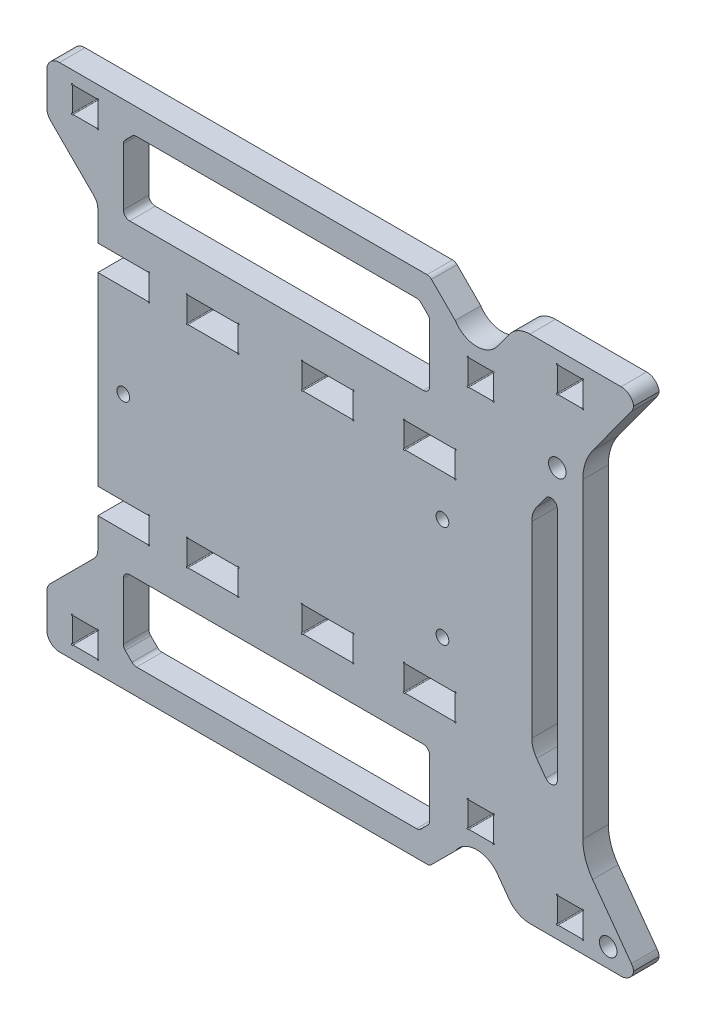
SolidWorks part; units mm, degrees
ref_plane "Front Plane" through (0, 0, 0) normal (0, 0, 1) x (1, 0, 0)
ref_plane "Top Plane" through (0, 0, 0) normal (0, 1, 0) x (1, 0, 0)
ref_plane "Right Plane" through (0, 0, 0) normal (1, 0, 0) x (0, 0, -1)
sketch "Sketch1" plane through (0, 0, 0) normal (0, 0, 1) x (1, 0, 0)
  line L0 (83.672, 0) -> (-43.8164, 0) construction
  line L1 (10.525, 38.1) -> (10.525, -38.1) construction
  line L2 (-27.575, 38.1) -> (48.625, 38.1)
  line L3 (99.425, -63.5) -> (99.425, -60.325)
  line L4 (99.425, -60.325) -> (74.025, -25.4)
  line L5 (-27.575, -63.5) -> (48.625, -63.5)
  line L6 (-27.575, 38.1) -> (-27.575, 54.5197)
  line L7 (48.625, 38.1) -> (48.625, 54.5197)
  line L8 (-24.9447, 57.15) -> (45.9947, 57.15)
  line L9 (-27.575, 63.5) -> (48.625, 63.5)
  line L10 (-33.925, 57.15) -> (-33.925, -57.15)
  line L11 (-27.575, 63.5) -> (-33.925, 57.15)
  line L12 (-24.9447, 57.15) -> (-27.575, 54.5197)
  line L13 (99.425, 63.5) -> (99.425, 60.325)
  line L14 (-23.0849, 59.0099) -> (-29.4349, 52.6599) construction
  line L15 (99.425, 60.325) -> (74.025, 25.4)
  line L16 (74.025, 25.4) -> (74.025, -25.4)
  line L17 (48.625, -38.1) -> (48.625, -54.5197)
  line L18 (-27.575, -38.1) -> (48.625, -38.1)
  line L19 (-24.9447, -57.15) -> (45.9947, -57.15)
  line L20 (-24.9447, -57.15) -> (-27.575, -54.5197)
  line L21 (-27.575, -38.1) -> (-27.575, -54.5197)
  line L22 (-27.575, -63.5) -> (-33.925, -57.15)
  line L23 (48.625, -63.5) -> (54.975, -57.15)
  line L24 (48.625, 63.5) -> (54.975, 57.15)
  line L25 (70.3271, -63.5) -> (99.425, -63.5)
  line L26 (45.9947, 57.15) -> (48.625, 54.5197)
  line L27 (45.9947, -57.15) -> (48.625, -54.5197)
  line L28 (70.3271, 63.5) -> (65.7089, 57.15)
  line L29 (70.3271, 63.5) -> (99.425, 63.5)
  line L30 (78.8831, 75.2646) -> (53.4831, 40.3396) construction
  line L31 (54.975, -42.3909) -> (54.975, -57.15)
  line L32 (70.3271, -63.5) -> (65.7089, -57.15)
  line L34 (48.625, -63.5) -> (54.975, -57.15)
  line L35 (65.7089, 57.15) -> (54.975, 42.3909)
  line L36 (54.975, 42.3909) -> (54.975, 57.15)
  line L37 (65.7089, -57.15) -> (54.975, -42.3909)
  point P7 (-27.575, 0)
  point P21 (74.025, 0)
  point P22 (-33.925, 0)
  dimension "D1" = 25.4
  dimension "D2" = 76.2
  dimension "D3" = 127
  dimension "D4" = 6.35
  dimension "D7" = 3.175
  dimension "D8" = 25.4
  dimension "D9" = 25.4
  dimension "D6" = 6.35
extrude "Boss-Extrude1" add sketch "Sketch1" along normal blind 6.35 contours L23 L32 L25 L3 L4 L16 L15 L13 L29 L28 L24 L9 L11 L10 L22 L5 L8 L26 L7 L2 L6 L12 L27 L19 L20 L21 L18 L17 region at (27.1557, 0, 0)
fillet "Fillet1" radius 6.35 4 edges at (70.3271, 63.5, 3.175) (70.3271, -63.5, 3.175) (54.975, -42.3909, 3.175) (54.975, 42.3909, 3.175)
fillet "Fillet3" radius 3.175 4 edges at (99.425, 63.5, 3.175) (99.425, 60.325, 3.175) (99.425, -60.325, 3.175) (99.425, -63.5, 3.175)
fillet "Fillet4" radius 6.35 2 edges at (74.025, -25.4, 3.175) (74.025, 25.4, 3.175)
fillet "Fillet7" radius 1.5875 4 edges at (-27.575, -38.1, 3.175) (48.625, -38.1, 3.175) (48.625, 38.1, 3.175) (-27.575, 38.1, 3.175)
fillet "Fillet8" radius 1.5875 2 edges at (48.625, -63.5, 3.175) (48.625, 63.5, 3.175)
fillet "Fillet9" radius 1.5875 8 edges at (-27.575, 54.5197, 3.175) (-24.9447, 57.15, 3.175) (-27.575, -54.5197, 3.175) (-24.9447, -57.15, 3.175) (45.9947, -57.15, 3.175) (48.625, -54.5197, 3.175) (48.625, 54.5197, 3.175) (45.9947, 57.15, 3.175)
sketch "Sketch2" plane through (0, 0, 6.35) normal (0, 0, 1) x (1, 0, 0)
  line L0 (-33.925, 0) -> (74.025, 0) construction
  line L1 (-33.925, 57.15) -> (-33.925, -57.15) construction
  line L2 (74.025, 23.3351) -> (74.025, -23.3351) construction
  line L3 (48.625, 39.6875) -> (48.625, 53.8622) construction
  line L4 (58.3484, 50.8) -> (64.3016, 50.8)
  line L5 (58.15, 50.6016) -> (58.15, 44.6484)
  line L6 (58.3484, 44.45) -> (64.3016, 44.45)
  line L7 (64.5, 50.6016) -> (64.5, 44.6484)
  line L8 (64.5, -50.6016) -> (64.5, -44.6484)
  line L9 (58.3484, -50.8) -> (64.3016, -50.8)
  line L10 (58.15, -50.6016) -> (58.15, -44.6484)
  line L11 (58.3484, -44.45) -> (64.3016, -44.45)
  arc A0 (58.3484, 50.8) -> (58.15, 50.6016) centre (58.15, 50.8) ccw
  arc A1 (64.5, 50.6016) -> (64.3016, 50.8) centre (64.5, 50.8) ccw
  arc A2 (64.3016, 44.45) -> (64.5, 44.6484) centre (64.5, 44.45) ccw
  arc A3 (58.15, 44.6484) -> (58.3484, 44.45) centre (58.15, 44.45) ccw
  arc A4 (64.3016, -44.45) -> (64.5, -44.6484) centre (64.5, -44.45) cw
  arc A5 (64.5, -50.6016) -> (64.3016, -50.8) centre (64.5, -50.8) cw
  arc A6 (58.3484, -50.8) -> (58.15, -50.6016) centre (58.15, -50.8) cw
  arc A7 (58.15, -44.6484) -> (58.3484, -44.45) centre (58.15, -44.45) cw
  point P10 (48.625, 46.7748)
  dimension "D5" = 0.3969
  dimension "D6" = 0.3969
  dimension "D7" = 0.3969
  dimension "D8" = 0.3969
  dimension "D1" = 6.35
  dimension "D2" = 6.35
  dimension "D3" = 50.8
  dimension "D4" = 9.525
extrude "Cut-Extrude1" cut sketch "Sketch2" against normal through all
sketch "Sketch5" plane through (0, 0, 6.35) normal (0, 0, 1) x (1, 0, 0)
  line L0 (-33.925, 29.3675) -> (74.025, 29.3675) construction
  line L1 (-33.925, 57.15) -> (-33.925, -57.15) construction
  line L2 (74.025, 23.3351) -> (74.025, -23.3351) construction
  line L3 (-25.9875, 38.1) -> (47.0375, 38.1) construction
  line L4 (-33.925, 23.0175) -> (74.025, 23.0175) construction
  line L5 (-33.925, 0) -> (74.025, 0) construction
  line L6 (-11.5016, 29.3675) -> (0.8016, 29.3675)
  line L7 (-11.7, 29.169) -> (-11.7, 23.2159)
  line L8 (-11.5016, 23.0175) -> (0.8016, 23.0175)
  line L9 (1, 29.169) -> (1, 23.2159)
  line L10 (42.4734, 29.3675) -> (54.7766, 29.3675)
  line L11 (42.275, 29.169) -> (42.275, 23.2159)
  line L12 (42.4734, 23.0175) -> (54.7766, 23.0175)
  line L13 (54.975, 29.169) -> (54.975, 23.2159)
  line L14 (29.3766, 29.3675) -> (17.0734, 29.3675)
  line L15 (29.575, 29.169) -> (29.575, 23.2159)
  line L16 (29.3766, 23.0175) -> (17.0734, 23.0175)
  line L17 (16.875, 29.169) -> (16.875, 23.2159)
  line L18 (-21.4234, 29.3675) -> (-33.925, 29.3675)
  line L19 (-21.225, 29.169) -> (-21.225, 23.2159)
  line L20 (-21.4234, 23.0175) -> (-33.925, 23.0175)
  line L21 (-33.925, 29.3675) -> (-33.925, 23.0175)
  line L22 (-33.925, -29.3675) -> (-33.925, -23.0175)
  line L23 (-21.4234, -23.0175) -> (-33.925, -23.0175)
  line L24 (-21.225, -29.169) -> (-21.225, -23.2159)
  line L25 (-21.4234, -29.3675) -> (-33.925, -29.3675)
  line L26 (16.875, -29.169) -> (16.875, -23.2159)
  line L27 (29.3766, -23.0175) -> (17.0734, -23.0175)
  line L28 (29.575, -29.169) -> (29.575, -23.2159)
  line L29 (29.3766, -29.3675) -> (17.0734, -29.3675)
  line L30 (54.975, -29.169) -> (54.975, -23.2159)
  line L31 (42.4734, -23.0175) -> (54.7766, -23.0175)
  line L32 (42.275, -29.169) -> (42.275, -23.2159)
  line L33 (42.4734, -29.3675) -> (54.7766, -29.3675)
  line L34 (1, -29.169) -> (1, -23.2159)
  line L35 (-11.5016, -23.0175) -> (0.8016, -23.0175)
  line L36 (-11.7, -29.169) -> (-11.7, -23.2159)
  line L37 (-11.5016, -29.3675) -> (0.8016, -29.3675)
  line L38 (-33.925, 26.1925) -> (54.975, 26.1925) construction
  arc A0 (-21.225, 29.169) -> (-21.4234, 29.3675) centre (-21.225, 29.3675) ccw
  arc A1 (-11.5016, 29.3675) -> (-11.7, 29.169) centre (-11.7, 29.3675) ccw
  arc A2 (1, 29.169) -> (0.8016, 29.3675) centre (1, 29.3675) ccw
  arc A3 (29.575, 29.169) -> (29.3766, 29.3675) centre (29.575, 29.3675) ccw
  arc A4 (17.0734, 29.3675) -> (16.875, 29.169) centre (16.875, 29.3675) ccw
  arc A5 (54.975, 29.169) -> (54.7766, 29.3675) centre (54.975, 29.3675) ccw
  arc A6 (42.4734, 29.3675) -> (42.275, 29.169) centre (42.275, 29.3675) ccw
  arc A7 (17.0734, 23.0175) -> (16.875, 23.2159) centre (16.875, 23.0175) cw
  arc A8 (29.575, 23.2159) -> (29.3766, 23.0175) centre (29.575, 23.0175) cw
  arc A9 (42.4734, 23.0175) -> (42.275, 23.2159) centre (42.275, 23.0175) cw
  arc A10 (54.975, 23.2159) -> (54.7766, 23.0175) centre (54.975, 23.0175) cw
  arc A11 (1, 23.2159) -> (0.8016, 23.0175) centre (1, 23.0175) cw
  arc A12 (-11.5016, 23.0175) -> (-11.7, 23.2159) centre (-11.7, 23.0175) cw
  arc A13 (-21.225, 23.2159) -> (-21.4234, 23.0175) centre (-21.225, 23.0175) cw
  arc A14 (-21.225, -23.2159) -> (-21.4234, -23.0175) centre (-21.225, -23.0175) ccw
  arc A15 (-11.5016, -23.0175) -> (-11.7, -23.2159) centre (-11.7, -23.0175) ccw
  arc A16 (1, -23.2159) -> (0.8016, -23.0175) centre (1, -23.0175) ccw
  arc A17 (54.975, -23.2159) -> (54.7766, -23.0175) centre (54.975, -23.0175) ccw
  arc A18 (42.4734, -23.0175) -> (42.275, -23.2159) centre (42.275, -23.0175) ccw
  arc A19 (29.575, -23.2159) -> (29.3766, -23.0175) centre (29.575, -23.0175) ccw
  arc A20 (17.0734, -23.0175) -> (16.875, -23.2159) centre (16.875, -23.0175) ccw
  arc A21 (42.4734, -29.3675) -> (42.275, -29.169) centre (42.275, -29.3675) cw
  arc A22 (54.975, -29.169) -> (54.7766, -29.3675) centre (54.975, -29.3675) cw
  arc A23 (17.0734, -29.3675) -> (16.875, -29.169) centre (16.875, -29.3675) cw
  arc A24 (29.575, -29.169) -> (29.3766, -29.3675) centre (29.575, -29.3675) cw
  arc A25 (1, -29.169) -> (0.8016, -29.3675) centre (1, -29.3675) cw
  arc A26 (-11.5016, -29.3675) -> (-11.7, -29.169) centre (-11.7, -29.3675) cw
  arc A27 (-21.225, -29.169) -> (-21.4234, -29.3675) centre (-21.225, -29.3675) cw
  dimension "D11" = 0.3969
  dimension "D12" = 0.3969
  dimension "D13" = 0.3969
  dimension "D14" = 0.3969
  dimension "D15" = 0.3969
  dimension "D16" = 0.3969
  dimension "D17" = 0.3969
  dimension "D1" = 8.7325
  dimension "D3" = 12.7
  dimension "D4" = 12.7
  dimension "D5" = 41.275
  dimension "D6" = 34.925
  dimension "D7" = 12.7
  dimension "D8" = 12.7
  dimension "D9" = 50.8
  dimension "D10" = 0
  dimension "D2" = 6.35
extrude "Cut-Extrude4" cut sketch "Sketch5" against normal through all
sketch "Sketch6" plane through (0, 0, 6.35) normal (0, 0, 1) x (1, 0, 0)
  line L0 (80.375, 34.1312) -> (80.375, -34.1312)
  line L1 (98.8177, 59.49) -> (75.2395, 27.07) construction
  line L2 (98.8177, -59.49) -> (75.2395, -27.07) construction
  line L3 (74.025, 23.3351) -> (74.025, -23.3351) construction
  line L4 (86.725, 34.1312) -> (86.725, -34.1312)
  line L5 (86.725, 34.1312) -> (86.725, 42.8625)
  line L6 (86.725, 42.8625) -> (80.375, 34.1312)
  line L7 (86.725, -34.1312) -> (86.725, -42.8625)
  line L8 (86.725, -42.8625) -> (80.375, -34.1312)
  dimension "D1" = 6.35
  dimension "D2" = 6.35
extrude "Boss-Extrude2" add sketch "Sketch6" against normal blind 6.35
fillet "Fillet10" radius 1.5875 2 edges at (80.375, -34.1312, 3.175) (80.375, 34.1312, 3.175)
fillet "Fillet11" radius 12.7 2 edges at (86.725, 42.8625, 3.175) (86.725, -42.8625, 3.175)
hole_wizard "11/64 (0.17188) Diameter Hole1" positions "Sketch8" profile "Sketch7" hole size "11/64" standard "ANSI Inch" end condition through all
sketch "Sketch8" plane through (0, 0, 6.35) normal (0, 0, 1) x (1, 0, 0)
  line L1 (-33.925, -29.3675) -> (-33.925, -57.15) construction
  line L2 (73.5606, 63.5) -> (96.25, 63.5) construction
  point P0 (80.375, 38.1)
  dimension "D1" = 25.4
  dimension "D2" = 114.3
sketch "Sketch7" plane through (80.375, 38.1, 6.35) normal (1, 0, 0) x (0, -1, 0)
  line L0 (0, 0) -> (0, 6.35)
  line L1 (0, 6.35) -> (2.1829, 6.35)
  line L2 (2.1829, 6.35) -> (2.1829, 0)
  line L5 (2.1829, 0) -> (0, 0)
  line L11 (0, -6.35) -> (0, 107.95) construction
  dimension "Thru Hole Dia." = 4.3658
  dimension "Thru Hole Depth" = 6.35
sketch "Sketch10" plane through (0, 0, 6.35) normal (0, 0, 1) x (1, 0, 0)
  line L0 (51.8, 63.5) -> (51.8, -63.5) construction
  line L1 (-27.575, 63.5) -> (47.9674, 63.5) construction
  line L2 (-27.575, -63.5) -> (47.9674, -63.5) construction
  line L3 (23.225, 29.3675) -> (23.225, -29.3675) construction
  line L4 (29.3766, 29.3675) -> (17.0734, 29.3675) construction
  line L5 (17.0734, -29.3675) -> (29.3766, -29.3675) construction
  line L6 (-27.575, 63.5) -> (-27.575, -63.5) construction
  line L7 (-33.925, 0) -> (74.025, 0) construction
  line L8 (-33.925, 23.0175) -> (-33.925, -23.0175) construction
  line L9 (74.025, 23.3351) -> (74.025, -23.3351) construction
  circle A0 centre (51.8, 12.7) radius 1.5875
  circle A1 centre (51.8, -12.7) radius 1.5875
  circle A2 centre (-27.575, 0) radius 1.5875
  dimension "D3" = 3.175
  dimension "D5" = 79.375
  dimension "D1" = 28.575
  dimension "D2" = 79.375
  dimension "D4" = 12.7
extrude "Cut-Extrude6" cut sketch "Sketch10" against normal through all
sketch "Sketch11" plane through (0, 0, 6.35) normal (0, 0, 1) x (1, 0, 0)
  line L0 (-62.0481, -60.325) -> (124.8486, -60.325) construction
  line L1 (-27.575, -63.5) -> (47.9674, -63.5) construction
  line L2 (-27.575, -63.5) -> (-33.925, -57.15)
  line L3 (-33.925, -57.15) -> (-33.925, -50.8)
  line L4 (-33.925, -50.8) -> (-33.925, -38.1)
  line L5 (-46.625, -50.8) -> (-46.625, -63.5)
  line L6 (-46.625, -63.5) -> (-27.575, -63.5)
  line L7 (-46.625, -50.8) -> (-33.925, -38.1)
  line L8 (-33.925, -29.3675) -> (-33.925, -57.15) construction
  line L9 (-46.625, 63.5) -> (-27.575, 63.5)
  line L10 (-33.925, 0) -> (74.025, 0) construction
  line L11 (-46.625, 50.8) -> (-46.625, 63.5)
  line L12 (-33.925, 23.0175) -> (-33.925, -23.0175) construction
  line L13 (74.025, 23.3351) -> (74.025, -23.3351) construction
  line L14 (-46.625, 50.8) -> (-33.925, 38.1)
  line L15 (-33.925, 57.15) -> (-33.925, 50.8)
  line L16 (-27.575, 63.5) -> (-33.925, 57.15)
  line L17 (-33.925, 50.8) -> (-33.925, 38.1)
  point P2 (10.1962, -63.5)
  dimension "D1" = 3.175
  dimension "D2" = 12.7
  dimension "D3" = 12.7
extrude "Boss-Extrude4" add sketch "Sketch11" against normal blind 6.35
sketch "Sketch12" plane through (0, 0, 6.35) normal (0, 0, 1) x (1, 0, 0)
  line L0 (73.5606, -63.5) -> (96.25, -63.5) construction
  line L1 (86.5266, -60.325) -> (80.5734, -60.325)
  line L2 (86.725, -60.1266) -> (86.725, -54.1734)
  line L3 (86.5266, -53.975) -> (80.5734, -53.975)
  line L4 (80.375, -60.1266) -> (80.375, -54.1734)
  line L5 (-33.925, -29.3675) -> (-33.925, -38.1) construction
  line L6 (-33.925, 0) -> (74.025, 0) construction
  line L7 (86.725, 60.1266) -> (86.725, 54.1734)
  line L8 (86.5266, 60.325) -> (80.5734, 60.325)
  line L9 (80.375, 60.1266) -> (80.375, 54.1734)
  line L10 (86.5266, 53.975) -> (80.5734, 53.975)
  line L11 (83.55, -60.325) -> (-33.7266, -60.325) construction
  line L12 (-34.1234, -60.325) -> (-54.5439, -60.325) construction
  line L13 (-34.1234, -60.325) -> (-40.0766, -60.325)
  line L14 (-33.925, -60.1266) -> (-33.925, -54.1734)
  line L15 (-34.1234, -53.975) -> (-40.0766, -53.975)
  line L16 (-40.275, -60.1266) -> (-40.275, -54.1734)
  line L17 (-34.1234, 60.325) -> (-40.0766, 60.325)
  line L18 (-33.925, 60.1266) -> (-33.925, 54.1734)
  line L19 (-40.275, 60.1266) -> (-40.275, 54.1734)
  line L20 (-34.1234, 53.975) -> (-40.0766, 53.975)
  arc A0 (-40.275, 60.1266) -> (-40.0766, 60.325) centre (-40.275, 60.325) cw
  arc A1 (80.5734, -53.975) -> (80.375, -54.1734) centre (80.375, -53.975) ccw
  arc A2 (86.725, -54.1734) -> (86.5266, -53.975) centre (86.725, -53.975) ccw
  arc A3 (80.375, -60.1266) -> (80.5734, -60.325) centre (80.375, -60.325) ccw
  arc A4 (86.5266, -60.325) -> (86.725, -60.1266) centre (86.725, -60.325) ccw
  arc A5 (86.5266, 60.325) -> (86.725, 60.1266) centre (86.725, 60.325) cw
  arc A6 (80.375, 60.1266) -> (80.5734, 60.325) centre (80.375, 60.325) cw
  arc A7 (80.5734, 53.975) -> (80.375, 54.1734) centre (80.375, 53.975) cw
  arc A8 (86.725, 54.1734) -> (86.5266, 53.975) centre (86.725, 53.975) cw
  arc A9 (-40.0766, -53.975) -> (-40.275, -54.1734) centre (-40.275, -53.975) ccw
  arc A10 (-33.925, -54.1734) -> (-34.1234, -53.975) centre (-33.925, -53.975) ccw
  arc A11 (-34.1234, -60.325) -> (-33.925, -60.1266) centre (-33.925, -60.325) ccw
  arc A12 (-40.275, -60.1266) -> (-40.0766, -60.325) centre (-40.275, -60.325) ccw
  arc A13 (-34.1234, 60.325) -> (-33.925, 60.1266) centre (-33.925, 60.325) cw
  arc A14 (-33.925, 54.1734) -> (-34.1234, 53.975) centre (-33.925, 53.975) cw
  arc A15 (-40.0766, 53.975) -> (-40.275, 54.1734) centre (-40.275, 53.975) cw
  point P4 (84.9053, -63.5)
  dimension "D5" = 0.3969
  dimension "D6" = 0.3969
  dimension "D7" = 0.3969
  dimension "D8" = 0.3969
  dimension "D12" = 0.3969
  dimension "D13" = 0.3969
  dimension "D14" = 0.3969
  dimension "D15" = 0.3969
  dimension "D1" = 6.35
  dimension "D2" = 6.35
  dimension "D3" = 3.175
  dimension "D4" = 114.3
  dimension "D9" = 6.35
  dimension "D10" = 6.35
  dimension "D11" = 120.65
extrude "Cut-Extrude7" cut sketch "Sketch12" against normal blind 6.35
fillet "Fillet12" radius 3.175 6 edges at (-46.625, 63.5, 3.175) (-46.625, 50.8, 3.175) (-33.925, 38.1, 3.175) (-46.625, -63.5, 3.175) (-46.625, -50.8, 3.175) (-33.925, -38.1, 3.175)
hole_wizard "11/64 (0.17188) Diameter Hole2" positions "Sketch14" profile "Sketch13" hole size "11/64" standard "ANSI Inch" end condition through all
sketch "Sketch14" plane through (0, 0, 0) normal (0, 0, -1) x (-1, 0, 0)
  line L0 (-73.5606, -63.5) -> (-96.25, -63.5) construction
  point P0 (-93.0328, -58.7375)
  dimension "D1" = 4.7625
  dimension "D2" = 6.35
sketch "Sketch13" plane through (93.0328, -58.7375, 0) normal (1, 0, 0) x (0, 1, 0)
  line L0 (0, 0) -> (0, 6.35)
  line L1 (0, 6.35) -> (2.1829, 6.35)
  line L2 (2.1829, 6.35) -> (2.1829, 0)
  line L5 (2.1829, 0) -> (0, 0)
  line L11 (0, -6.35) -> (0, 107.95) construction
  dimension "Thru Hole Dia." = 4.3658
  dimension "Thru Hole Depth" = 6.35
